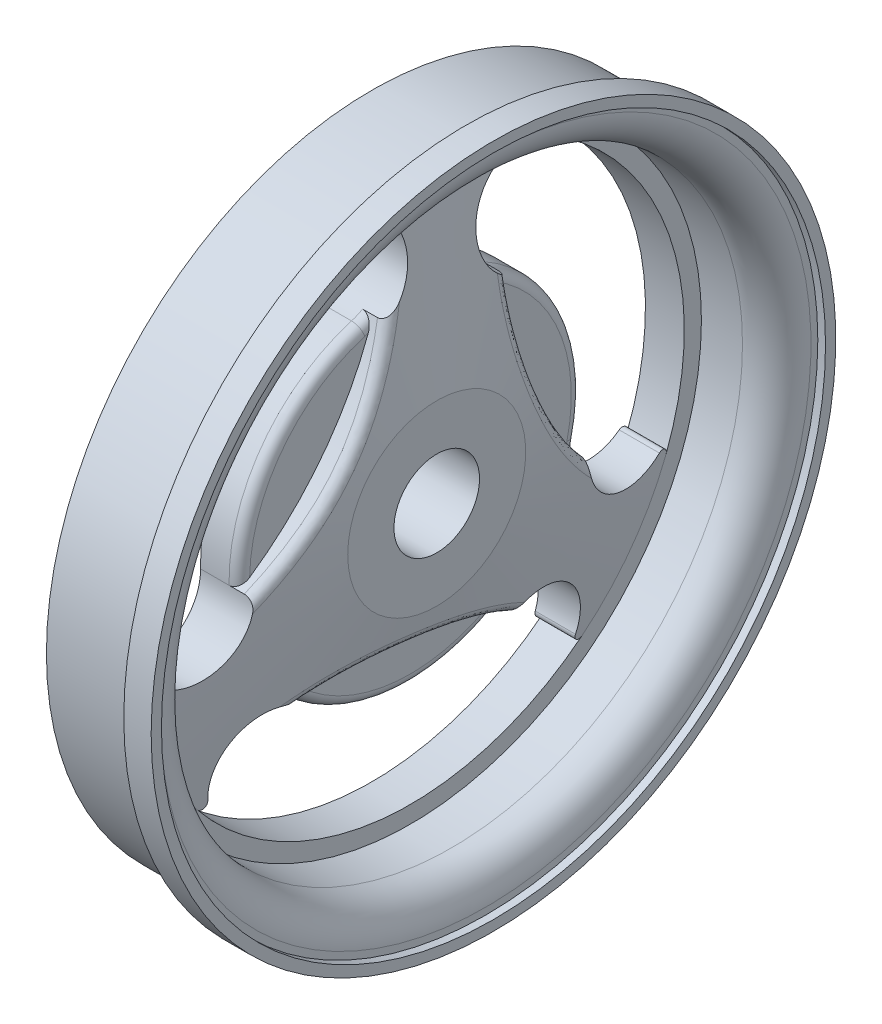
SolidWorks part; units mm, degrees
ref_plane "Front Plane" through (0, 0, 0) normal (0, 0, 1) x (1, 0, 0)
ref_plane "Top Plane" through (0, 0, 0) normal (0, 1, 0) x (1, 0, 0)
ref_plane "Right Plane" through (0, 0, 0) normal (1, 0, 0) x (0, 0, -1)
sketch "Sketch1" plane through (0, 0, 0) normal (0, 1, 0) x (1, 0, 0)
  line L0 (-3.4663, 0) -> (3.8569, 0) construction
  line L2 (2.76, 10) -> (2.76, 9.5)
  line L3 (2.76, 9.5) -> (0, 9.5)
  line L4 (0, 9.5) -> (0, 0)
  line L5 (0, 0) -> (1.9023, 0)
  line L7 (2.76, 10) -> (3.26, 10)
  line L8 (3.26, 10) -> (3.56, 10)
  line L9 (3.56, 10) -> (3.56, 9.7)
  line L10 (3.56, 9.7) -> (3.3346, 9.7)
  line L15 (1.6346, 8.5) -> (1.1346, 8.5)
  line L16 (1.1346, 8.5) -> (1.1346, 8)
  line L17 (1.1346, 8) -> (1.9023, 2.6)
  line L18 (1.9023, 2.6) -> (1.9023, 0)
  line L20 (1.6346, 8.5) -> (2.3346, 8.5)
  line L21 (3.3346, 9.5) -> (3.3346, 9.7)
  arc A2 (3.3346, 9.5) -> (2.3346, 8.5) centre (2.3346, 9.5) cw
  point P21 (2.1346, 8.5)
  point P23 (3.3346, 7.4)
  dimension "D6" = 0.5
  dimension "D5" = 1
  dimension "D1" = 0.5
  dimension "D2" = 19
  dimension "D3" = 0.3
  dimension "D4" = 0.3
  dimension "D7" = 1
  dimension "D8" = 1
  dimension "D11" = 20
  dimension "D12" = 2.76
  dimension "D13" = 3.26
  dimension "D14" = 0.5
  dimension "D15" = 0.5
  dimension "D17" = 2.6
revolve "Revolve1" add sketch "Sketch1" angle 360 about L0
sketch "Sketch2" plane through (1.9023, 0, 0) normal (1, 0, 0) x (0, 0, -1)
  circle A2 centre (-0.5637, -0.2494) radius 7 construction
  arc A22 (4.8622, -1.1659) -> (2.4071, 4.3824) centre (0, 0) ccw
  circle A24 centre (0, 0) radius 8
  arc A25 (7.4637, -2.8798) -> (2.8882, 7.4604) centre (0, 0) ccw
  arc A26 (2.8609, 7.173) -> (2.4071, 4.3824) centre (3.1292, 5.6972) ccw
  arc A27 (4.8622, -1.1659) -> (7.2326, -2.7067) centre (6.3208, -1.5156) ccw
  arc A28 (2.8609, 7.173) -> (2.8882, 7.4604) centre (2.8341, 7.3206) ccw
  arc A29 (7.4637, -2.8798) -> (7.2326, -2.7067) centre (7.3237, -2.8258) ccw
  arc A30 (-6.2259, -5.0238) -> (5.0168, -6.2315) centre (0, 0) ccw
  arc A31 (4.7815, -6.0641) -> (5.0168, -6.2315) centre (4.9228, -6.1147) ccw
  arc A32 (4.7815, -6.0641) -> (2.5917, -4.2758) centre (3.3693, -5.5586) ccw
  arc A33 (-3.4408, -3.6278) -> (2.5917, -4.2758) centre (0, 0) ccw
  arc A34 (-3.4408, -3.6278) -> (-5.9604, -4.9102) centre (-4.473, -4.7162) ccw
  arc A35 (-6.2259, -5.0238) -> (-5.9604, -4.9102) centre (-6.1091, -4.9296) ccw
  arc A36 (-1.2378, 7.9037) -> (-7.905, -1.2289) centre (0, 0) ccw
  arc A37 (-7.6424, -1.1089) -> (-7.905, -1.2289) centre (-7.7568, -1.2059) ccw
  arc A38 (-7.6424, -1.1089) -> (-4.9989, -0.1066) centre (-6.4985, -0.1386) ccw
  arc A39 (-1.4214, 4.7937) -> (-4.9989, -0.1066) centre (0, 0) ccw
  arc A40 (-1.4214, 4.7937) -> (-1.2722, 7.6169) centre (-1.8478, 6.2318) ccw
  arc A41 (-1.2378, 7.9037) -> (-1.2722, 7.6169) centre (-1.2146, 7.7555) ccw
  point P36 (0, 0)
  point P43 (0, 0)
  dimension "D1" = 0
  dimension "D2" = 0.3
  dimension "D3" = 0.3
  dimension "D4" = 5
  dimension "D5" = 3
extrude "Cut-Extrude1" cut sketch "Sketch2" against normal through all
sketch "Sketch4" plane through (1.9023, 0, 0) normal (1, 0, 0) x (0, 0, -1)
  circle A0 centre (0, 0) radius 1.25
  dimension "D1" = 2.5
extrude "Cut-Extrude3" cut sketch "Sketch4" against normal up to surface (1.9023 mm away) up to face at (0, 0, 9.5)
sketch "Sketch6" plane through (1.1346, 0, 0) normal (1, 0, 0) x (0, 0, -1)
  arc A0 (2.4071, 4.3824) -> (4.8208, -1.5156) centre (11.7022, 4.7434) ccw
  arc A1 (4.8622, -1.1659) -> (7.2326, -2.7067) centre (6.3208, -1.5156) ccw construction
  arc A2 (4.8622, -1.1659) -> (2.4071, 4.3824) centre (0, 0) ccw construction
  arc A3 (4.8622, -1.1659) -> (2.4071, 4.3824) centre (0, 0) ccw
  arc A4 (4.8622, -1.1659) -> (4.8208, -1.5156) centre (6.3208, -1.5156) ccw
  arc A5 (-3.4408, -3.6278) -> (2.5917, -4.2758) centre (0, 0) ccw
  arc A6 (2.5917, -4.2758) -> (-3.723, -3.4171) centre (-1.7432, -12.5061) ccw
  arc A7 (-3.4408, -3.6278) -> (-3.723, -3.4171) centre (-4.473, -4.7162) ccw
  arc A8 (-1.4214, 4.7937) -> (-4.9989, -0.1066) centre (0, 0) ccw
  arc A9 (-4.9989, -0.1066) -> (-1.0978, 4.9328) centre (-9.959, 7.7627) ccw
  arc A10 (-1.4214, 4.7937) -> (-1.0978, 4.9328) centre (-1.8478, 6.2318) ccw
  point P23 (0, 0)
  dimension "D1" = 3
extrude "Cut-Extrude5" cut sketch "Sketch6" along normal blind 10.5
fillet "Fillet1" radius 0.3 6 edges at (1.1346, 4.8537, 1.2555) (1.1346, 2.9482, 4.0383) (1.1346, -1.3395, -4.8312) (1.1346, -3.5142, 3.5757) (1.1346, 2.0232, -4.5724) (1.1346, -4.9714, 0.534)
fillet "Fillet2" radius 0.3 3 edges at (1.7858, 1.894, -2.8473) (1.7858, 1.5188, 3.0639) (1.7858, -3.4128, -0.2167)
